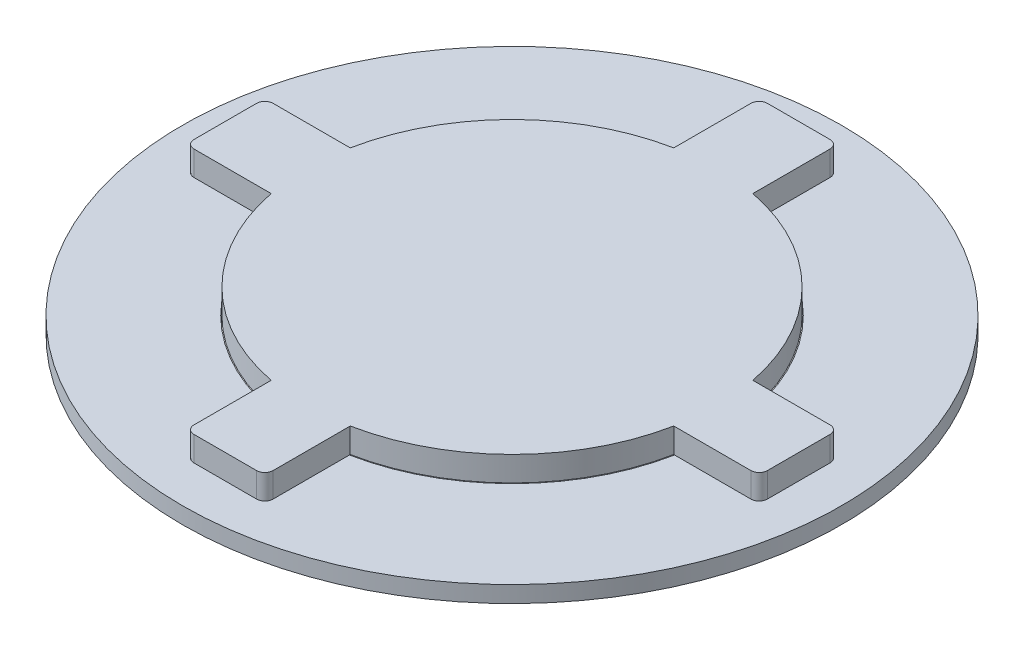
SolidWorks part; units mm, degrees
ref_plane "Alzado" through (0, 0, 0) normal (0, 0, 1) x (1, 0, 0)
ref_plane "Planta" through (0, 0, 0) normal (0, 1, 0) x (1, 0, 0)
ref_plane "Vista lateral" through (0, 0, 0) normal (1, 0, 0) x (0, 0, -1)
sketch "Croquis5" plane through (0, 0, 0) normal (0, 1, 0) x (1, 0, 0)
  circle A0 centre (0, 0) radius 24.9
  dimension "D1" = 49.8
extrude "Saliente-Extruir3" add sketch "Croquis5" along normal blind 3
sketch "Croquis6" plane through (0, 0, 0) normal (0, -1, 0) x (1, 0, 0)
  line L1 (33.8, 4.8) -> (-33.8, 4.8)
  line L2 (34.8, 3.8) -> (34.8, -3.8)
  line L3 (33.8, -4.8) -> (-33.8, -4.8)
  line L4 (-34.8, 3.8) -> (-34.8, -3.8)
  line L5 (34.8, 4.8) -> (-34.8, -4.8) construction
  line L6 (34.8, -4.8) -> (-34.8, 4.8) construction
  line L10 (3.8, -34.8) -> (-3.8, -34.8)
  line L11 (4.8, -33.8) -> (4.8, 33.8)
  line L12 (3.8, 34.8) -> (-3.8, 34.8)
  line L13 (-4.8, -33.8) -> (-4.8, 33.8)
  arc A0 (-3.8, -34.8) -> (-4.8, -33.8) centre (-3.8, -33.8) cw
  arc A1 (33.8, 4.8) -> (34.8, 3.8) centre (33.8, 3.8) cw
  arc A2 (34.8, -3.8) -> (33.8, -4.8) centre (33.8, -3.8) cw
  arc A3 (-33.8, -4.8) -> (-34.8, -3.8) centre (-33.8, -3.8) cw
  arc A4 (-33.8, 4.8) -> (-34.8, 3.8) centre (-33.8, 3.8) ccw
  arc A5 (4.8, -33.8) -> (3.8, -34.8) centre (3.8, -33.8) cw
  arc A6 (4.8, 33.8) -> (3.8, 34.8) centre (3.8, 33.8) ccw
  arc A7 (-4.8, 33.8) -> (-3.8, 34.8) centre (-3.8, 33.8) cw
  point P0 (0, 0)
  point P13 (0, 0)
  point P34 (0, 0)
  circle M5 centre (0, 0) radius 24.9
  dimension "D4" = 1
  dimension "D1" = 69.6
  dimension "D2" = 9.6
extrude "Saliente-Extruir4" add sketch "Croquis6" against normal blind 3 contours L1 L4 L3 M5 | M5 | L3 L2 L1 M5 | M5 region at (29.75, 0, 0) region at (0, 0, 29.75) region at (-29.75, 0, 0) region at (0, 0, -29.75)
sketch "Croquis7" plane through (0, 0, 0) normal (0, -1, 0) x (1, 0, 0)
  circle A0 centre (0, 0) radius 40
  dimension "D1" = 80
extrude "Saliente-Extruir5" add sketch "Croquis7" along normal blind 2
sketch "Croquis8" plane through (0, -2, 0) normal (0, -1, 0) x (1, 0, 0)
  line L0 (2.5, -30) -> (-2.5, -30)
  line L1 (30, 2.5) -> (-30, 2.5)
  line L2 (30, 2.5) -> (30, -2.5)
  line L3 (30, -2.5) -> (-30, -2.5)
  line L4 (-30, 2.5) -> (-30, -2.5)
  line L5 (30, 2.5) -> (-30, -2.5) construction
  line L6 (30, -2.5) -> (-30, 2.5) construction
  line L7 (2.5, -30) -> (2.5, 30)
  line L8 (2.5, 30) -> (-2.5, 30)
  line L9 (-2.5, -30) -> (-2.5, 30)
  circle A0 centre (0, 0) radius 20
  circle A1 centre (0, 0) radius 25
  point P0 (0, 0)
  point P13 (0, 0)
  dimension "D3" = 40
  dimension "D4" = 50
  dimension "D1" = 60
  dimension "D2" = 5
extrude "Cortar-Extruir3" cut sketch "Croquis8" against normal blind 2 contours A1 L9 L0 L7 | L9 A1 L7 A0 | L9 A0 L7 L3 | L9 L3 L7 L1 | L7 A0 L9 L1 | L7 A1 L9 A0 | A1 L7 L8 L9 | L3 A0 L1 L7 | L3 A1 L1 A0 | A1 L3 L2 L1 | L1 A0 L3 L9 | L1 A1 L3 A0 | A1 L1 L4 L3 | L9 A1 L1 A0 | L1 A1 L7 A0 | L7 A1 L3 A0 | L3 A1 L9 A0 region at (0, -2, -27.479) region at (0, -2, -22.453) region at (14.8009, -2, -14.8009) region at (-14.8009, -2, -14.8009) region at (0, -2, -11.224) region at (27.479, -2, 0) region at (22.453, -2, 0) region at (-22.453, -2, 0) region at (-27.479, -2, 0) region at (11.224, -2, 0) region at (0, -2, 0) region at (-11.224, -2, 0) region at (-14.8009, -2, 14.8009) region at (0, -2, 11.224) region at (14.8009, -2, 14.8009) region at (0, -2, 22.453) region at (0, -2, 27.479)
sketch "Croquis9" plane through (0, 0, 0) normal (0, -1, 0) x (1, 0, 0)
  line L0 (-30, 0) -> (30, 0) construction
  line L1 (-30, 2.5) -> (-30, -2.5) construction
  line L2 (30, 2.5) -> (30, -2.5) construction
  line L3 (0, -30) -> (0, 30) construction
  line L4 (2.5, -30) -> (-2.5, -30) construction
  line L5 (2.5, 30) -> (-2.5, 30) construction
  circle A0 centre (0, 0) radius 22.5 construction
  circle A1 centre (0, 0) radius 2
  dimension "D1" = 45
  dimension "4" = 4
extrude "Cortar-Extruir4" cut sketch "Croquis9" against normal blind 1
